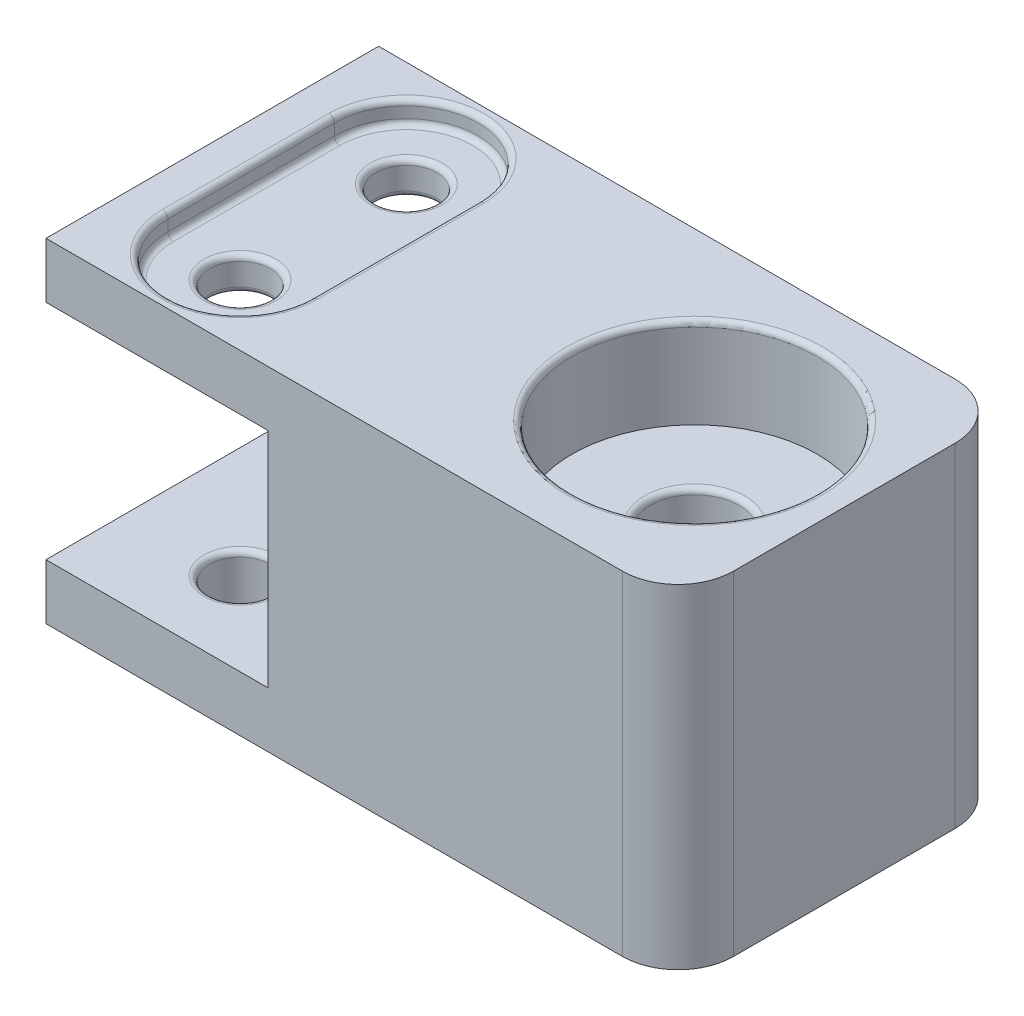
SolidWorks part; units mm, degrees
ref_plane "Front Plane" through (0, 0, 0) normal (0, 0, 1) x (1, 0, 0)
ref_plane "Top Plane" through (0, 0, 0) normal (0, 1, 0) x (1, 0, 0)
ref_plane "Right Plane" through (0, 0, 0) normal (1, 0, 0) x (0, 0, -1)
sketch "Sketch4" plane through (0, 0, 0) normal (0, 1, 0) x (1, 0, 0)
  line L1 (-28.5, -15) -> (28.5, -15)
  line L2 (-28.5, -15) -> (-28.5, 15)
  line L3 (-28.5, 15) -> (28.5, 15)
  line L4 (28.5, -15) -> (28.5, 15)
  line L5 (-28.5, -15) -> (28.5, 15) construction
  line L6 (-28.5, 15) -> (28.5, -15) construction
  point P0 (0, 0)
  dimension "D1" = 57
  dimension "D2" = 30
extrude "Boss-Extrude2" add sketch "Sketch4" along normal blind 5
sketch "Sketch5" plane through (0, 5, 0) normal (0, 1, 0) x (1, 0, 0)
  line L0 (-28.5, -15) -> (28.5, -15) construction
  line L1 (28.5, 15) -> (-8.5, 15)
  line L2 (28.5, 15) -> (28.5, -15)
  line L3 (28.5, -15) -> (-8.5, -15)
  line L4 (-8.5, 15) -> (-8.5, -15)
  line L5 (28.5, 15) -> (-8.5, -15) construction
  line L6 (28.5, -15) -> (-8.5, 15) construction
  line L7 (-28.5, 15) -> (-28.5, -15) construction
  point P4 (10, 0)
  dimension "D1" = 20
extrude "Boss-Extrude3" add sketch "Sketch5" along normal blind 20.1
sketch "Sketch6" plane through (0, 25.1, 0) normal (0, 1, 0) x (1, 0, 0)
  line L0 (28.5, -15) -> (28.5, 15) construction
  line L1 (28.5, 15) -> (-8.5, 15) construction
  line L3 (-8.5, -15) -> (28.5, -15) construction
  line L5 (-8.5, 15) -> (-28.5, 15) construction
  line L6 (-28.5, 15) -> (-28.5, -15) construction
  line L7 (-28.5, -15) -> (-8.5, -15) construction
  line L8 (28.5, -15) -> (28.5, 15)
  line L9 (28.5, 15) -> (-8.5, 15)
  line L11 (-8.5, -15) -> (28.5, -15)
  line L13 (-8.5, 15) -> (-28.5, 15)
  line L14 (-28.5, 15) -> (-28.5, -15)
  line L15 (-28.5, -15) -> (-8.5, -15)
extrude "Boss-Extrude4" add sketch "Sketch6" along normal blind 5
sketch "Sketch7" plane through (0, 30.1, 0) normal (0, 1, 0) x (1, 0, 0)
  line L0 (-28.5, -15) -> (28.5, -15) construction
  line L1 (-28.5, 15) -> (-28.5, -15) construction
  line L2 (-28.5, 0) -> (28.5, 0) construction
  line L3 (28.5, -15) -> (28.5, 15) construction
  circle A0 centre (-18.5, -7.5) radius 2.75
  circle A1 centre (-18.5, 7.5) radius 2.75
  dimension "D1" = 5.5
  dimension "D2" = 7.5
  dimension "D3" = 10
extrude "Cut-Extrude3" cut sketch "Sketch7" against normal through all
fillet "Fillet5" radius 0.5 8 edges at (-18.5, 5, -10.25) (-18.5, 0, -10.25) (-18.5, 5, 4.75) (-18.5, 0, 10.25) (-18.5, 25.1, -4.75) (-18.5, 30.1, -10.25) (-18.5, 25.1, 10.25) (-18.5, 30.1, 10.25)
sketch "Sketch8" plane through (0, 30.1, 0) normal (0, 1, 0) x (1, 0, 0)
  line L0 (-8.5, 15) -> (-8.5, -15) construction
  line L1 (-8.5, 15) -> (-8.5, -15) construction
  line L2 (28.5, -15) -> (28.5, 15) construction
  circle A1 centre (15, 0) radius 11.049
  dimension "D1" = 22.098
  dimension "D2" = 13.5
extrude "Cut-Extrude4" cut sketch "Sketch8" against normal blind 8.128 contours A1
fillet "Fillet6" radius 5 2 edges at (28.5, 15.05, -15) (28.5, 15.05, 15)
sketch "Sketch11" plane through (0, 0, 0) normal (0, -1, 0) x (1, 0, 0)
  circle A1 centre (15, 0) radius 11.049 construction
  circle A2 centre (15, 0) radius 11.049
extrude "Cut-Extrude5" cut sketch "Sketch11" against normal blind 8.128
sketch "Sketch12" plane through (0, 8.128, 0) normal (0, -1, 0) x (1, 0, 0)
  circle A0 centre (15, 0) radius 4.025
  circle A1 centre (15, 0) radius 11.049
  circle A4 centre (15, 0) radius 11.049
  dimension "D2" = 8.05
  dimension "D1" = 0
extrude "Cut-Extrude6" cut sketch "Sketch12" against normal through all contours A0 region at (15, 8.128, 0)
fillet "Fillet7" radius 0.5 4 edges at (15, 30.1, 11.049) (15, 8.128, -4.025) (15, 21.972, 4.025) (15, 0, -11.049)
sketch "Sketch13" plane through (0, 30.1, 0) normal (0, 1, 0) x (1, 0, 0)
  line L0 (-25, -7.5) -> (-25, 7.5)
  line L1 (-12, -7.5) -> (-12, 7.5)
  arc A0 (-25, -7.5) -> (-12, -7.5) centre (-18.5, -7.5) ccw
  arc A1 (-12, 7.5) -> (-25, 7.5) centre (-18.5, 7.5) ccw
  point P4 (0, 0)
  point P8 (0, 0)
  point P9 (-14.4073, 2.4503)
  dimension "D1" = 13
extrude "Cut-Extrude7" cut sketch "Sketch13" against normal blind 2
fillet "Fillet8" radius 0.5 10 edges at (-12, 28.1, 0) (-18.5, 28.1, 14) (-25, 28.1, 0) (-12, 30.1, 0) (-18.5, 30.1, 14) (-25, 30.1, 0) (-18.5, 28.1, -14) (-18.5, 30.1, -14) (-18.5, 28.1, 10.25) (-18.5, 28.1, -4.75)
